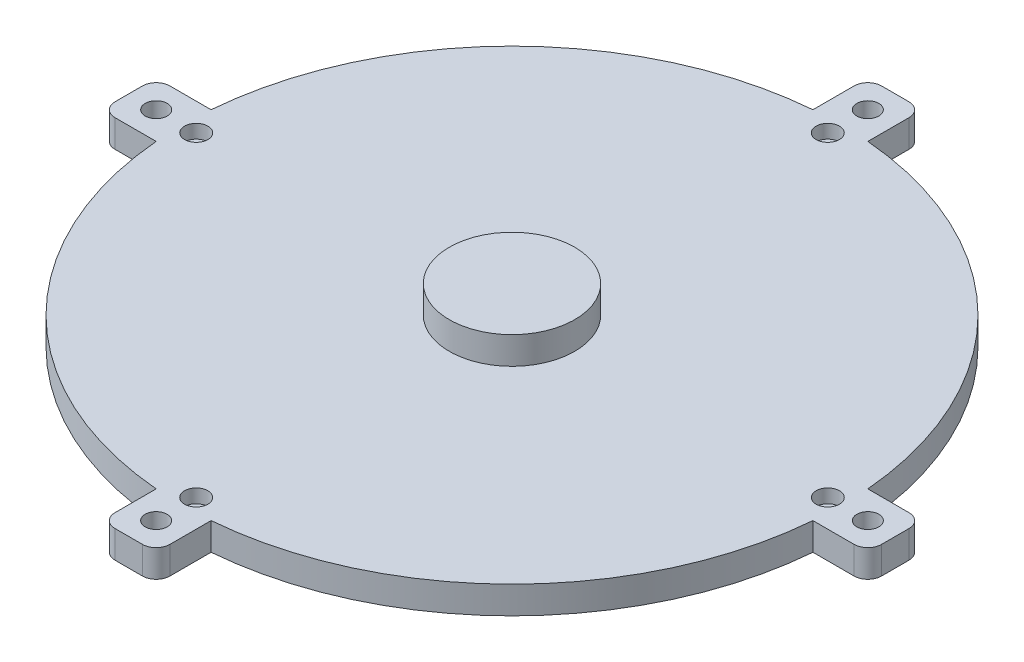
SolidWorks part; units mm, degrees
ref_plane "Front Plane" through (0, 0, 0) normal (0, 0, 1) x (1, 0, 0)
ref_plane "Top Plane" through (0, 0, 0) normal (0, 1, 0) x (1, 0, 0)
ref_plane "Right Plane" through (0, 0, 0) normal (1, 0, 0) x (0, 0, -1)
sketch "Sketch5" plane through (0, 0, 0) normal (1, 0, 0) x (0, 0, -1)
  line L0 (22.85, 10) -> (120, 10)
  line L1 (0, 0) -> (120, 0)
  line L2 (0, 0) -> (0, 20)
  line L4 (120, 0) -> (120, 10)
  line L5 (0, 20) -> (22.85, 20)
  line L8 (22.85, 20) -> (22.85, 10)
  line L9 (0, 0) -> (0, 65.0916) construction
  point P2 (121.1611, 10)
  dimension "D1" = 45.7
  dimension "D2" = 240
  dimension "D3" = 10
  dimension "D4" = 10
revolve "Revolve1" add sketch "Sketch5" angle 360 about L9
sketch "Sketch6" plane through (0, 10, 0) normal (0, 1, 0) x (1, 0, 0)
  line L1 (-10, 119.5826) -> (10, 119.5826)
  line L2 (-10, 119.5826) -> (-10, 139.5826)
  line L3 (-10, 139.5826) -> (10, 139.5826)
  line L4 (10, 119.5826) -> (10, 139.5826)
  circle A0 centre (0, 0) radius 120 construction
  point P6 (-34.4246, 114.9563)
  point P7 (37.8807, 113.8642)
  dimension "D1" = 20
  dimension "D2" = 20
extrude "Boss-Extrude3" add sketch "Sketch6" against normal through all
fillet "Fillet1" radius 5 2 edges at (-10, 5, -139.5826) (10, 5, -139.5826)
hole_wizard "Ø8.0mm Dowel Hole1" positions "3DSketch1" profile "Sketch7" hole size "Ø8.0" standard "ISO" end condition through all
sketch3d "3DSketch1"
  line L0 (0, 10, -139.5826) -> (0, 10, -129.5826) construction
  line L1 (5, 10, -139.5826) -> (-5, 10, -139.5826) construction
  point P0 (0, 10, -129.5826)
  dimension "D1" = 10
sketch "Sketch7" plane through (0, 10, -129.5826) normal (1, 0, 0) x (0, 0, 1)
  line L0 (0, 0) -> (0, 10)
  line L1 (0, 10) -> (4, 10)
  line L2 (4, 10) -> (4, 0)
  line L5 (4, 0) -> (0, 0)
  line L11 (0, -6.35) -> (0, 107.95) construction
  dimension "Thru Hole Dia." = 8
  dimension "Thru Hole Depth" = 10
pattern_circular "CirPattern1" count 4 over 360 about axis through (0, 0, 0) along (0, -1, 0) of "Fillet1", "Boss-Extrude3", "Ø8.0mm Dowel Hole1" reverse direction yes
sketch "Sketch8" plane through (0, 10, 0) normal (0, 1, 0) x (1, 0, 0)
  line L0 (0, 115) -> (0, 0) construction
  circle A0 centre (0, 115) radius 4.25
  dimension "D2" = 8.5
  dimension "D1" = 115
extrude "Cut-Extrude1" cut sketch "Sketch8" against normal blind 5
pattern_circular "CirPattern2" count 4 over 360 about axis through (0, 0, 0) along (0, -1, 0) of "Cut-Extrude1" reverse direction yes
